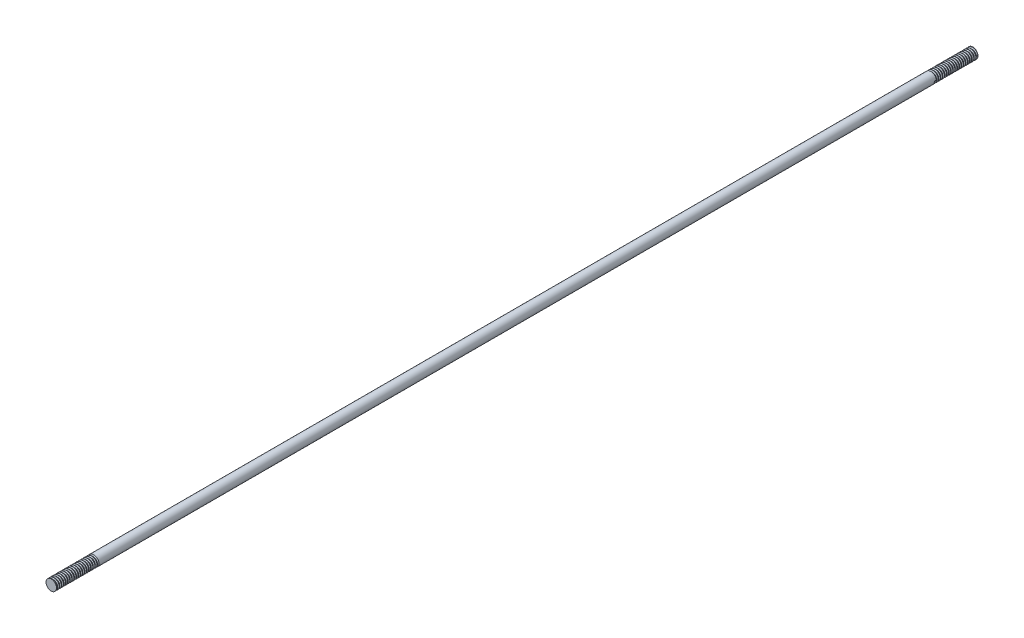
SolidWorks part; units mm, degrees
ref_plane "Front Plane" through (0, 0, 0) normal (0, 0, 1) x (1, 0, 0)
ref_plane "Top Plane" through (0, 0, 0) normal (0, 1, 0) x (1, 0, 0)
ref_plane "Right Plane" through (0, 0, 0) normal (1, 0, 0) x (0, 0, -1)
sketch "Sketch1" plane through (0, 0, 0) normal (0, 0, 1) x (1, 0, 0)
  circle A0 centre (0, 0) radius 3.175
  dimension "D1" = 6.35
extrude "Boss-Extrude1" add sketch "Sketch1" along normal blind 558.8
thread "Thread2" pitch 1.27 method cut profile "Thread Profile1" start angle 2, offset 0, length 25.4, pitch 1.27, diameter 6.35
ref_plane "Plane1" through (3.1731, 0.1108, 0) normal (0.0349, -0.9994, 0) x (0.9994, 0.0349, 0)
sketch "Thread Profile1" plane through (3.1731, 0.1108, 0) normal (0.0349, -0.9994, 0) x (0.9994, 0.0349, 0)
  line L0 (0, 0) -> (0, 1.27) construction
  line L11 (0, 0) -> (0, 1.1112)
  line L12 (0, 1.1112) -> (-0.6874, 0.7144)
  line L13 (-0.6874, 0.7144) -> (-0.6874, 0.3969)
  line L15 (-0.6874, 0.3969) -> (0, 0)
  line L17 (-0.6874, 0.5556) -> (0, 0.5556) construction
  point P2 (0, 0)
  dimension "Pitch" = 1.27
  dimension "Profile_Angle" = 60
  dimension "Profile_Land" = 0.3175
  dimension "Profile_Height" = 0.6874
thread "Thread3" pitch 1.27 method cut profile "Thread Profile2" start angle 2, offset 0, length 25.4, pitch 1.27, diameter 6.35
ref_plane "Plane2" through (-3.1731, 0.1108, 558.8) normal (-0.0349, -0.9994, 0) x (-0.9994, 0.0349, 0)
sketch "Thread Profile2" plane through (-3.1731, 0.1108, 558.8) normal (-0.0349, -0.9994, 0) x (-0.9994, 0.0349, 0)
  line L0 (0, 0) -> (0, 1.27) construction
  line L11 (0, 0) -> (0, 1.1112)
  line L12 (0, 1.1112) -> (-0.6874, 0.7144)
  line L13 (-0.6874, 0.7144) -> (-0.6874, 0.3969)
  line L15 (-0.6874, 0.3969) -> (0, 0)
  line L17 (-0.6874, 0.5556) -> (0, 0.5556) construction
  point P2 (0, 0)
  dimension "Pitch" = 1.27
  dimension "Profile_Angle" = 60
  dimension "Profile_Land" = 0.3175
  dimension "Profile_Height" = 0.6874
ref_axis "Axis1" through (0, 0, 558.8) along (0, 0, -1)
